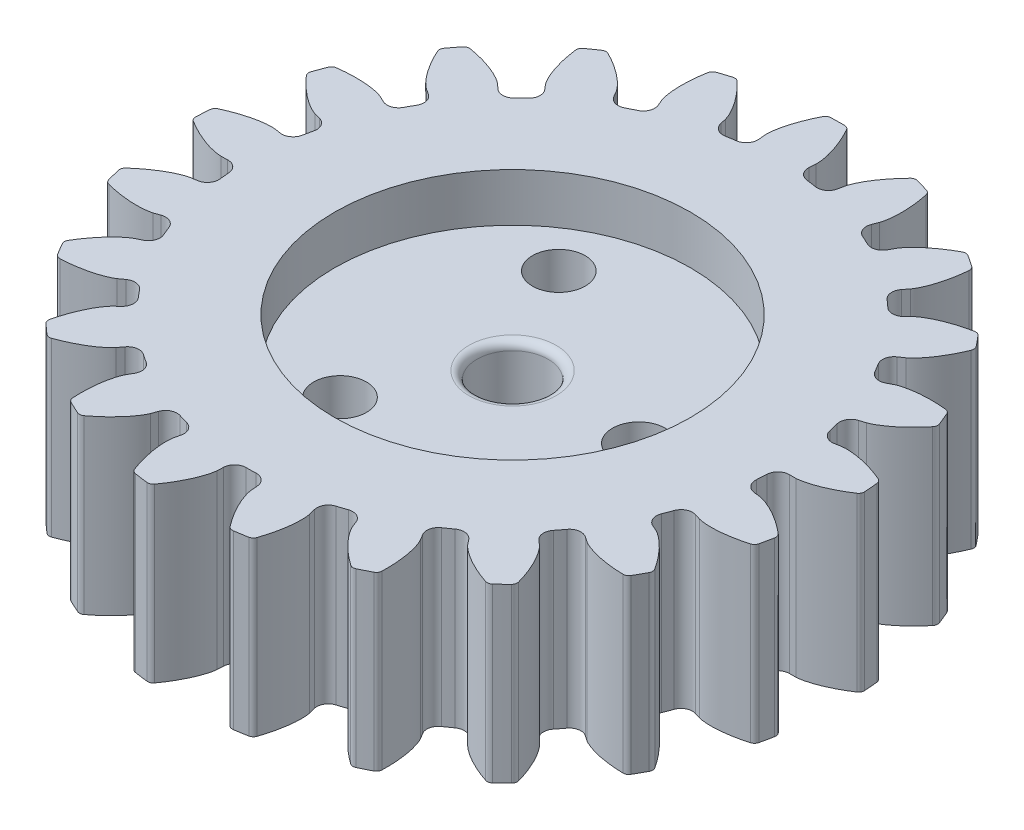
SolidWorks part; units mm, degrees
material "Acero aleado"
ref_plane "Alzado" through (0, 0, 0) normal (0, 0, 1) x (1, 0, 0)
ref_plane "Planta" through (0, 0, 0) normal (0, 1, 0) x (1, 0, 0)
ref_plane "Vista lateral" through (0, 0, 0) normal (1, 0, 0) x (0, 0, -1)
sketch "Croquis1" plane through (0, 0, 0) normal (0, 1, 0) x (1, 0, 0)
  line L0 (0, 0) -> (24.6669, 0)
  line L1 (0, 0) -> (26.2471, 0.3912) construction
  line L2 (0, 0) -> (28.6344, 2.5757)
  line L4 (0, 0) -> (28.6985, -1.7208)
  circle A0 centre (0, 0) radius 26.25 construction
  circle A1 centre (0, 0) radius 28.75
  circle A2 centre (0, 0) radius 24.6669
  circle A3 centre (0, 0) radius 28.75 construction
  circle A4 centre (0, 0) radius 23.125
  arc A6 (28.6985, -1.7208) -> (28.6996, 1.7022) centre (0, 0) ccw
  spline S0 degree 4 poles (24.6669, 0) (24.6735, 0.0001) (24.6918, 0.0006) (24.7264, 0.0025) (24.7829, 0.0071) (24.8548, 0.0151) (24.9476, 0.0278) (25.0567, 0.0459) (25.1763, 0.0691) (25.3062, 0.0978) (25.4354, 0.1295) (25.564, 0.1641) (25.6918, 0.2011) (25.8461, 0.249) (26.0306, 0.3107) (26.2453, 0.3889) (26.4876, 0.485) (26.7331, 0.5906) (26.9735, 0.7009) (27.2148, 0.8196) (27.4473, 0.9397) (27.6871, 1.0717) (27.9076, 1.1974) (28.1526, 1.3463) (28.3497, 1.4688) (28.6075, 1.6391) (28.7591, 1.7422) (28.9356, 1.8659) (29.0136, 1.9223) (29.0616, 1.957) knots 0 0 0 0 0 0.005377 0.015084 0.028532 0.04661 0.064855 0.092111 0.119476 0.146842 0.174209 0.201575 0.228941 0.256307 0.307035 0.361767 0.4165 0.471232 0.525964 0.580697 0.635429 0.690161 0.744894 0.799626 0.854358 0.909091 0.954545 1 1 1 1 1 construction
  spline S1 degree 4 poles (24.6669, 0) (24.6735, 0.0001) (24.6918, 0.0006) (24.7264, 0.0025) (24.7829, 0.0071) (24.8548, 0.0151) (24.9476, 0.0278) (25.0567, 0.0459) (25.1763, 0.0691) (25.3062, 0.0978) (25.4354, 0.1295) (25.564, 0.1641) (25.6918, 0.2011) (25.8461, 0.249) (26.0306, 0.3107) (26.2453, 0.3889) (26.4876, 0.485) (26.7331, 0.5906) (26.9735, 0.7009) (27.2148, 0.8196) (27.4473, 0.9397) (27.6871, 1.0717) (27.9076, 1.1974) (28.1526, 1.3463) (28.3497, 1.4688) (28.5516, 1.6022) (28.6496, 1.6681) (28.6996, 1.7022) knots 0 0 0 0 0 0.005377 0.015084 0.028532 0.04661 0.064855 0.092111 0.119476 0.146842 0.174209 0.201575 0.228941 0.256307 0.307035 0.361767 0.4165 0.471232 0.525964 0.580697 0.635429 0.690161 0.744894 0.799626 0.854358 0.909091 0.909091 0.909091 0.909091 0.909091
  dimension "D1" = 52.5
  dimension "D2" = 57.5
  dimension "D3" = 49.3339
  dimension "D4" = 46.25
  dimension "D5" = 8.571
  dimension "D6" = 4.286
extrude "Saliente-Extruir4" add sketch "Croquis1" along normal blind 15 contours L0 A4 L2 | L4 A4 L0 | A4 L0 A2 L2 | A2 S1 A1 L2 region at (15.396, 0, -0.6911) region at (15.4075, 0, 0.4615) region at (23.8722, 0, -1.0715) region at (26.3912, 0, -1.4582)
sketch "Croquis10" plane through (0, 15, 0) normal (0, 1, 0) x (1, 0, 0)
  line L0 (0, 0) -> (23.0835, -1.3841)
  line L1 (0, 0) -> (23.0835, -1.3841)
  line L2 (0, 0) -> (28.6344, 2.5757)
  line L3 (0, 0) -> (28.6344, 2.5757)
  line L4 (-10.15, 1.65) -> (10.15, 1.65)
  line L5 (-10, -1.5) -> (10, -1.5) construction
  line L6 (-10, -1.5) -> (-10, 1.5) construction
  line L7 (-10, 1.5) -> (10, 1.5) construction
  line L8 (10, -1.5) -> (10, 1.5) construction
  line L9 (-10, -1.5) -> (10, 1.5) construction
  line L10 (-10, 1.5) -> (10, -1.5) construction
  line L11 (10.15, -1.65) -> (10.15, 1.65)
  line L12 (-10.15, -1.65) -> (10.15, -1.65)
  line L13 (-10.15, -1.65) -> (-10.15, 1.65)
  circle A0 centre (0, 0) radius 23.125
  arc A2 (28.6996, 1.7022) -> (28.6344, 2.5757) centre (0, 0) ccw
  circle A7 centre (0, 0) radius 3 construction
  circle A8 centre (0, 0) radius 3.15
  arc A9 (28.6996, 1.7022) -> (28.6344, 2.5757) centre (0, 0) ccw
  spline S0 degree 4 poles (4.6481, 999.7911) (22.7503, 13.8395) (23.4033, 0.223) (24.0945, -0.0489) (24.7829, 0.0071) (24.8548, 0.0151) (24.9476, 0.0278) (25.0567, 0.0459) (25.1763, 0.0691) (25.3062, 0.0978) (25.4354, 0.1295) (25.564, 0.1641) (25.6918, 0.2011) (25.8461, 0.249) (26.0306, 0.3107) (26.2453, 0.3889) (26.4876, 0.485) (26.7331, 0.5906) (26.9735, 0.7009) (27.2148, 0.8196) (27.4473, 0.9397) (27.6871, 1.0717) (27.9076, 1.1974) (28.1526, 1.3463) (29.0466, 1.902) (31.6551, 3.7794) (3.8223, -15.0185) (854.5089, 565.6312) knots -0.521457 -0.521457 -0.521457 -0.521457 -0.521457 0.005377 0.015084 0.028532 0.04661 0.064855 0.092111 0.119476 0.146842 0.174209 0.201575 0.228941 0.256307 0.307035 0.361767 0.4165 0.471232 0.525964 0.580697 0.635429 0.690161 0.744894 0.799626 0.854358 1.68299 1.68299 1.68299 1.68299 1.68299 only from (24.6669, 0) to (28.6996, 1.7022)
  spline S1 degree 4 poles (24.6669, 0) (24.6735, 0.0001) (24.6918, 0.0006) (24.7264, 0.0025) (24.7829, 0.0071) (24.8548, 0.0151) (24.9476, 0.0278) (25.0567, 0.0459) (25.1763, 0.0691) (25.3062, 0.0978) (25.4354, 0.1295) (25.564, 0.1641) (25.6918, 0.2011) (25.8461, 0.249) (26.0306, 0.3107) (26.2453, 0.3889) (26.4876, 0.485) (26.7331, 0.5906) (26.9735, 0.7009) (27.2148, 0.8196) (27.4473, 0.9397) (27.6871, 1.0717) (27.9076, 1.1974) (28.1526, 1.3463) (28.3497, 1.4688) (28.5516, 1.6022) (28.6496, 1.6681) (28.6996, 1.7022) knots 0 0 0 0 0 0.005377 0.015084 0.028532 0.04661 0.064855 0.092111 0.119476 0.146842 0.174209 0.201575 0.228941 0.256307 0.307035 0.361767 0.4165 0.471232 0.525964 0.580697 0.635429 0.690161 0.744894 0.799626 0.854358 0.909091 0.909091 0.909091 0.909091 0.909091
  spline S3 degree 3 poles (17.6092, 0.01) (17.7752, 0.0086) (18.1032, 0.0814) (18.7425, 0.2684) (19.5069, 0.611) (20.3688, 1.1202) (20.9089, 1.5158) (21.1699, 1.7241) knots -0.002288 -0.002288 -0.002288 -0.002288 0.111468 0.225224 0.452736 0.680248 0.907761 0.907761 0.907761 0.907761
  line M6 (28.6344, 2.5757) -> (0, 0)
  line M7 (0, 0) -> (23.0835, -1.3841)
  dimension "D3" = 3
  dimension "D4" = 20
  dimension "D5" = 0.15
  dimension "D6" = 0.15
fillet "Redondeo5" radius 1 1 edges at (23.125, 7.5, 0)
fillet "Redondeo6" radius 0.5 1 edges at (28.6996, 7.5, -1.7022)
mirror "Simetría1" about plane through (0, 15, 0) normal (-0.0896, 0, -0.996) of "Redondeo6", "Saliente-Extruir4", "Redondeo5"
pattern_circular "MatrizC8" count 21 over 360 about axis through (0, 15, 0) along (0, -1, 0) reverse direction yes of bodies 160
extrude "Saliente-Extruir6" add sketch "Croquis10" against normal up to surface (15 mm away) contours M6 M7 | M6 M7 region at (2.0978, 15, -0.0313) region at (-0.0817, 15, 0.0012) up to face at (22.9112, 0, -2.0609)
sketch "Croquis11" plane through (0, 0, 0) normal (0, -1, 0) x (1, 0, 0)
  circle A0 centre (0, 0) radius 3.1
  circle A2 centre (0, 0) radius 10
  dimension "D1" = 6.2
  dimension "D2" = 20
extrude "Cortar-Extruir5" cut sketch "Croquis11" against normal through all contours A0 region at (0, 0, 0)
sketch "Croquis12" plane through (0, 0, 0) normal (0, -1, 0) x (1, 0, 0)
  circle A0 centre (0, 0) radius 6.5
  circle A1 centre (0, 0) radius 3.1 construction
  circle A2 centre (0, 0) radius 3.1
  dimension "D1" = 13
extrude "Saliente-Extruir7" add sketch "Croquis12" along normal blind 2
sketch "Croquis13" plane through (0, 15, 0) normal (0, 1, 0) x (1, 0, 0)
  line L0 (0, 0) -> (11, 0)
  circle A0 centre (11, 0) radius 2.3
  circle A1 centre (-5.5, -9.5263) radius 2.3
  circle A2 centre (-5.5, 9.5263) radius 2.3
  dimension "D1" = 4.6
  dimension "D2" = 11
  dimension "D3" = 3
extrude "Cortar-Extruir6" cut sketch "Croquis13" against normal blind 12 contours A2 | A0 | A1 | A1 | A2 region at (11, 15, 2.2349) region at (-5.5, 15, 9.5263) region at (-5.5, 15, -9.5263)
sketch "Croquis14" plane through (0, 15, 0) normal (0, 1, 0) x (1, 0, 0)
  circle A0 centre (0, 0) radius 15.5
  dimension "D1" = 31
extrude "Cortar-Extruir7" cut sketch "Croquis14" against normal blind 4.2
fillet "Redondeo7" radius 0.7 1 edges at (0, 10.8, 3.1)
equation "\"D4@Croquis10\"=\"Cvarilla\""
equation "\"D3@Croquis10\"=\"Avarilla\""
equation "\"D2@Croquis10\"=\"Dvarilla\""
equation "\"D4@Croquis1\"= \"df\""
equation "\"d\"= \"Z\" * \"m\""
equation "\"Z\"= 21"
equation "\"m\"= 2.5mm"
equation "\"da\"= ( \"d\" + \"m\" * 2 ) * 1mm"
equation "\"df\"= \"d\" - \"m\" * 2.5"
equation "\"alpha\"= 20°"
equation "\"db\"= ( \"d\" * cos ( \"alpha\" ) ) * 1mm"
equation "\"p\"= \"m\" * pi"
equation "\"s\"= \"m\" * pi / 2"
equation "\"rb\"= \"db\" / 2"
equation "\"ra\"= \"da\" / 2"
equation "\"t_max\"= sqr ( ( \"ra\" / \"rb\" ) ^ 2 - 1 )"
equation "\"theta\"= ( \"m\" / \"d\" * pi ) * 1rad"
equation "\"D1@Croquis1\"=\"d\""
equation "\"D2@Croquis1\"=\"da\""
equation "\"D3@Croquis1\"=\"db\""
equation "\"D5@Croquis1\"=360/(\"Z\"*2)"
equation "\"D6@Croquis1\"= \"theta\" / 2"
equation "\"b\"= 15mm"
equation "\"redon\"= \"m\" * 0.1"
equation "\"D1@Saliente-Extruir4\"=\"b\""
equation "\"offset\"= 0.15"
equation "\"D1@MatrizC8\"=\"Z\""
equation "\"Dvarilla\"= 6mm"
equation "\"Avarilla\"= 3mm"
equation "\"Bvarilla\"= 10mm"
equation "\"Cvarilla\"= 20mm"
equation "\"D1@Croquis11\"=6.2"
